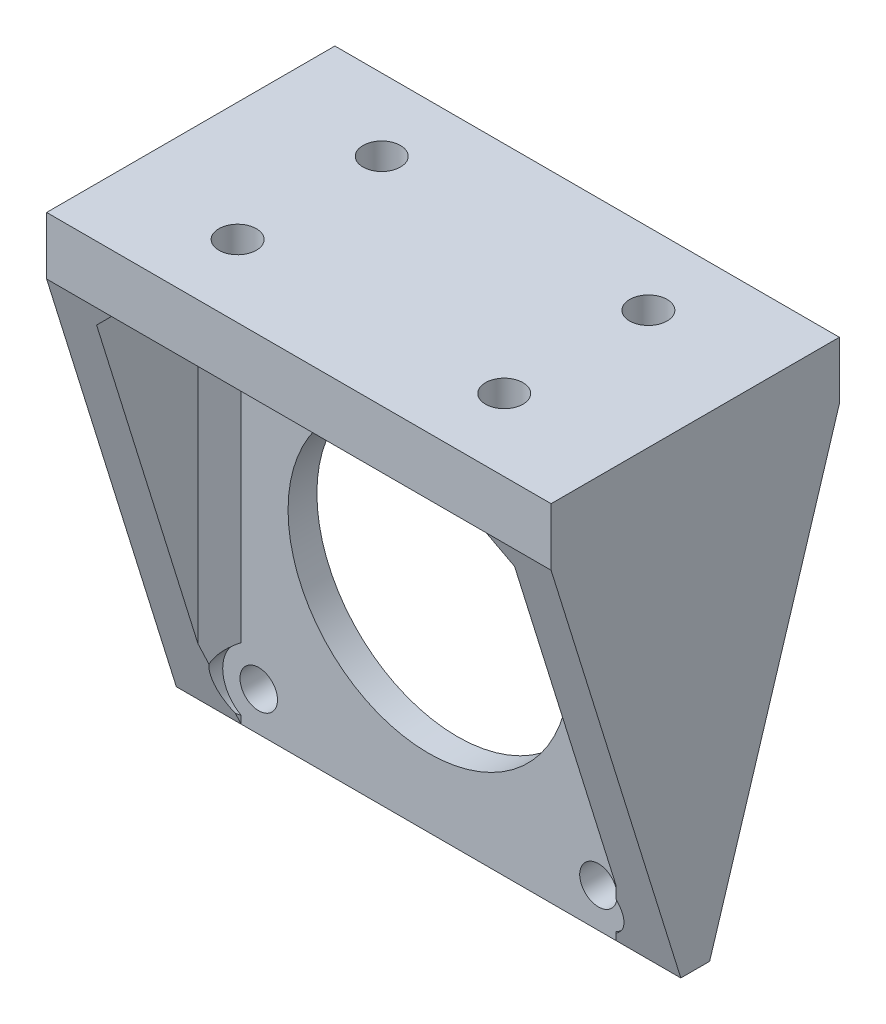
SolidWorks part; units mm, degrees
ref_plane "Спереди" through (0, 0, 0) normal (0, 0, 1) x (1, 0, 0)
ref_plane "Сверху" through (0, 0, 0) normal (0, 1, 0) x (1, 0, 0)
ref_plane "Справа" through (0, 0, 0) normal (1, 0, 0) x (0, 0, -1)
sketch "Эскиз1" plane through (0, 0, 0) normal (0, 0, 1) x (1, 0, 0)
  line L0 (29, -29) -> (29, 29)
  line L1 (-29, 29) -> (29, 29)
  line L2 (-29, 29) -> (-29, -29)
  line L3 (-29, -29) -> (29, -29)
  point P4 (-29, 0)
  dimension "D1" = 58
  dimension "D2" = 58
  dimension "D3" = 29
extrude "Бобышка-Вытянуть1" add sketch "Эскиз1" along normal blind 4
sketch "Эскиз6" plane through (0, 0, 4) normal (0, 0, 1) x (1, 0, 0)
  line L0 (-23.57, -23.57) -> (23.57, 23.57) construction
  circle A0 centre (0, 0) radius 19.5
  circle A1 centre (-23.57, 23.57) radius 2.6
  circle A2 centre (23.57, 23.57) radius 2.6
  circle A3 centre (-23.57, -23.57) radius 2.6
  circle A4 centre (23.57, -23.57) radius 2.6
  point P11 (0, 0)
  dimension "D1" = 39
  dimension "D2" = 5.2
  dimension "D3" = 5.2
  dimension "D4" = 5.2
  dimension "D5" = 5.2
  dimension "D7" = 47.14
  dimension "D6" = 47.14
extrude "Вырез-Вытянуть1" cut sketch "Эскиз6" against normal through all
sketch "Эскиз3" plane through (0, 29, 0) normal (0, 1, 0) x (1, 0, 0)
  line L10 (-29, -4) -> (-29, 0) construction
  line L11 (29, 0) -> (-29, 0) construction
  line L12 (29, -4) -> (-29, -4) construction
  line L15 (35, -22) -> (-35, -22)
  line L16 (35, -22) -> (35, 18)
  line L17 (35, 18) -> (-35, 18)
  line L18 (-35, -22) -> (-35, 18)
  line L19 (29, -4) -> (29, 0) construction
  dimension "D1" = 18
  dimension "D2" = 40
  dimension "D3" = 6
  dimension "D4" = 6
extrude "Бобышка-Вытянуть2" add sketch "Эскиз3" along normal blind 8
sketch "Эскиз5" plane through (29, 0, 0) normal (1, 0, 0) x (0, 0, -1)
  line L24 (-4, -29) -> (0, -29)
  line L25 (0, -29) -> (18, 29)
  line L30 (18, 29) -> (-22, 29)
  line L31 (-22, 29) -> (-4, -29)
extrude "Бобышка-Вытянуть3" add sketch "Эскиз5" along normal blind 6
mirror "Зеркальное отражение3" about plane through (0, 0, 0) normal (1, 0, 0) of "Бобышка-Вытянуть3"
sketch "Эскиз8" plane through (0, 29, 0) normal (0, 1, 0) x (1, 0, 0)
  line L1 (-29, -22) -> (29, -22) construction
  line L4 (0, -50) -> (0, 50) construction
  line L5 (-32.5, -2) -> (49967.5, -2) construction
  line L6 (-35, 18) -> (-35, -22) construction
  circle A20 centre (18.5, 8) radius 2.6
  circle A21 centre (-18.5, 8) radius 2.6
  circle A30 centre (18.5, -12) radius 2.6
  circle A31 centre (-18.5, -12) radius 2.6
  point P6 (19.304, -14.6298)
  point P12 (-19.304, -14.6298)
  point P20 (-35, -2)
  dimension "D1" = 5.2
  dimension "D2" = 10
extrude "Вырез-Вытянуть2" cut sketch "Эскиз8" along normal through all
sketch "Эскиз9" plane through (0, 29, 0) normal (0, -1, 0) x (1, 0, 0)
  circle A0 centre (-18.5, -8) radius 5
  circle A1 centre (18.5, -8) radius 5
  dimension "D1" = 10
  dimension "D2" = 10
extrude "Вырез-Вытянуть3" cut sketch "Эскиз9" against normal blind 3
chamfer "Фаска2" distance 3 angle 45 2 edges at (29, 0, 4) (-29, 0, 4)
chamfer "Фаска1" distance 3 angle 45 4 edges at (-29, 29, 14.5) (29, 29, 14.5) (29, 29, -9) (-29, 29, -9)
sketch "Эскиз11" plane through (0, 0, 4) normal (0, 0, 1) x (1, 0, 0)
  circle A0 centre (-23.57, 23.57) radius 5
  circle A1 centre (23.57, 23.57) radius 5
  circle A2 centre (23.57, -23.57) radius 5
  circle A3 centre (-23.57, -23.57) radius 5
  dimension "D1" = 10
  dimension "D2" = 10
  dimension "D3" = 10
  dimension "D4" = 10
extrude "Вырез-Вытянуть4" cut sketch "Эскиз11" along normal through all
